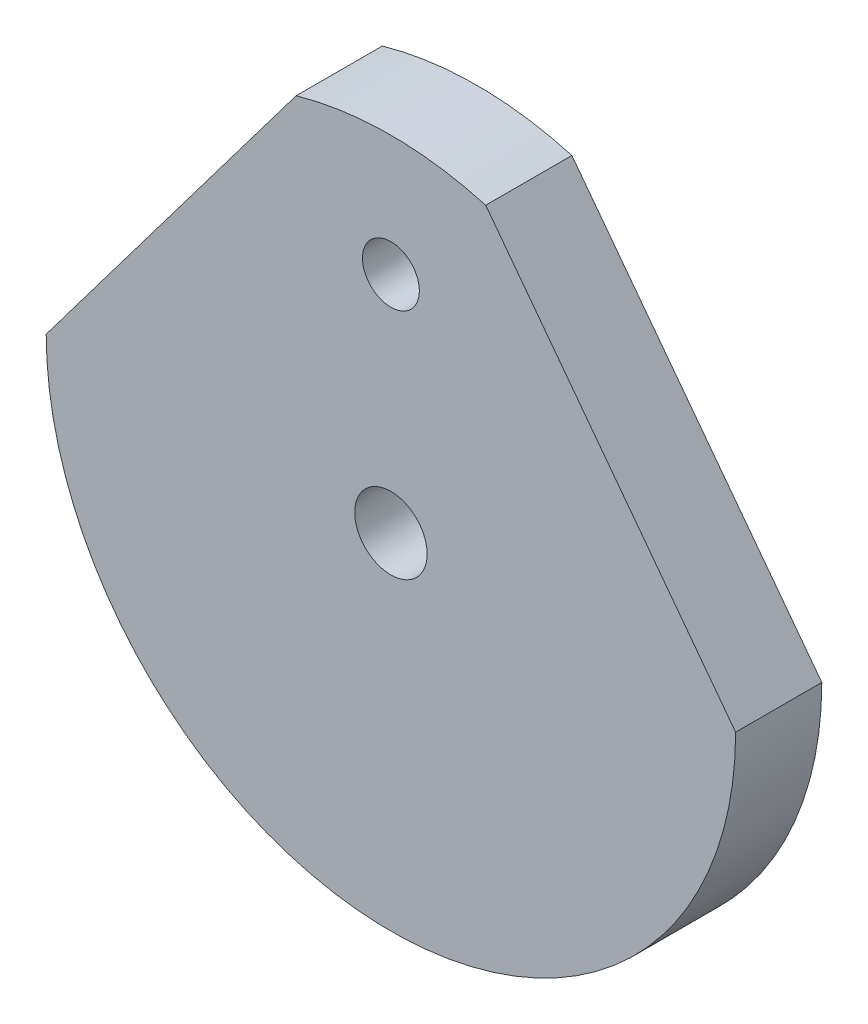
SolidWorks part; units mm, degrees
material "AISI 304"
ref_plane "Front Plane" through (0, 0, 0) normal (0, 0, 1) x (1, 0, 0)
ref_plane "Top Plane" through (0, 0, 0) normal (0, 1, 0) x (1, 0, 0)
ref_plane "Right Plane" through (0, 0, 0) normal (1, 0, 0) x (0, 0, -1)
sketch "Sketch1" plane through (0, 0, 0) normal (0, 0, 1) x (1, 0, 0)
  line L0 (-20, 0) -> (-5.5, 19.2289)
  line L1 (20, 0) -> (5.5, 19.2289)
  circle A0 centre (0, 0) radius 20
  dimension "D1" = 40
  dimension "D2" = 11
extrude "Boss-Extrude1" add sketch "Sketch1" along normal mid plane 5 contours L1 A0 L0 region at (0, -1.2467, 0)
sketch "Sketch2" plane through (0, 0, -2.5) normal (0, 0, -1) x (-1, 0, 0)
  circle A0 centre (0, 0) radius 5
  dimension "D1" = 10
extrude "Boss-Extrude2" add sketch "Sketch2" along normal blind 1
fillet "Fillet1" radius 1 1 edges at (-5, 0, -2.5)
sketch "Sketch3" plane through (0, 0, 2.5) normal (0, 0, 1) x (1, 0, 0)
  line L0 (0, 0) -> (0, 13)
  dimension "D1" = 13
hole_wizard "M5 Tapped Hole1" positions "3DSketch1" profile "Sketch4" tap size "M5" standard "ISO" end condition through all
sketch3d "3DSketch1"
  point P0 (0, 0, 2.5)
sketch "Sketch4" plane through (0, 0, 2.5) normal (1, 0, 0) x (0, -1, 0)
  line L0 (0, 0) -> (0, 6)
  line L1 (0, 6) -> (2.1, 6)
  line L2 (2.1, 6) -> (2.1, 0)
  line L5 (2.1, 0) -> (0, 0)
  line L11 (0, -6.35) -> (0, 107.95) construction
  dimension "Thru Tap Drill Dia." = 4.2
  dimension "Thru Tap Drill Depth" = 6
cosmetic thread "Hole Thread1"
hole_wizard "M4 Tapped Hole1" positions "3DSketch2" profile "Sketch5" tap size "M4" standard "ISO" end condition through all
sketch3d "3DSketch2"
  point P0 (0, 13, 2.5)
sketch "Sketch5" plane through (0, 13, 2.5) normal (1, 0, 0) x (0, -1, 0)
  line L0 (0, 0) -> (0, 6)
  line L1 (0, 6) -> (1.65, 6)
  line L2 (1.65, 6) -> (1.65, 0)
  line L5 (1.65, 0) -> (0, 0)
  line L11 (0, -6.35) -> (0, 107.95) construction
  dimension "Thru Tap Drill Dia." = 3.3
  dimension "Thru Tap Drill Depth" = 6
cosmetic thread "Hole Thread2"
